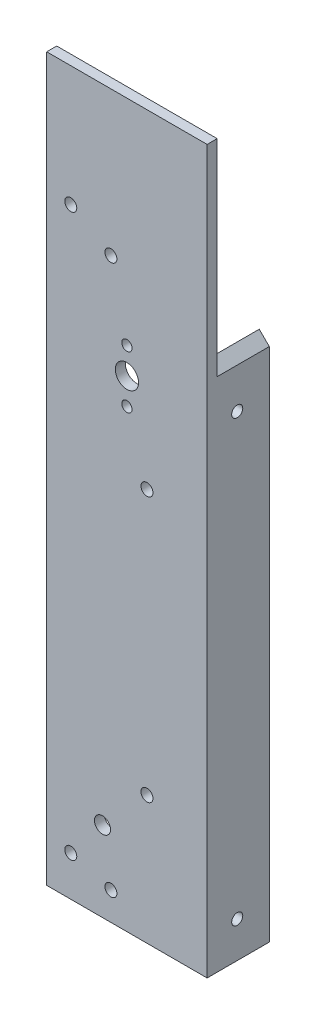
SolidWorks part; units mm, degrees
ref_plane "Front Plane" through (0, 0, 0) normal (0, 0, 1) x (1, 0, 0)
ref_plane "Top Plane" through (0, 0, 0) normal (0, 1, 0) x (1, 0, 0)
ref_plane "Right Plane" through (0, 0, 0) normal (1, 0, 0) x (0, 0, -1)
sketch "Sketch1" plane through (0, 0, 0) normal (0, 1, 0) x (1, 0, 0)
  line L0 (0, 0) -> (-50.8, 0)
  line L1 (-50.8, 0) -> (-50.8, 3.175)
  line L2 (-50.8, 3.175) -> (-3.175, 3.175)
  line L3 (-3.175, 3.175) -> (-3.175, 19.685)
  line L4 (-3.175, 19.685) -> (0, 19.685)
  line L5 (0, 19.685) -> (0, 0)
  dimension "D1" = 16.51
  dimension "D2" = 3.175
  dimension "D3" = 50.8
extrude "Boss-Extrude1" add sketch "Sketch1" along normal blind 203.2 contours L2 L3 L4 L5 L0 L1
sketch "Sketch4" plane through (0, 0, 0) normal (0, 0, 1) x (1, 0, 0)
  line L0 (0, 203.2) -> (0, 0) construction
  line L1 (-50.8, 214.122) -> (-57.2505, 214.122)
  line L2 (-50.8, 214.122) -> (0, 163.322)
  line L3 (-50.8, 203.2) -> (-50.8, 0) construction
  line L5 (14.4916, 163.322) -> (14.4916, 247.072)
  line L6 (14.4916, 247.072) -> (-57.2505, 247.072)
  line L7 (-57.2505, 247.072) -> (-57.2505, 214.122)
  line L9 (0, 163.322) -> (14.4916, 163.322)
  dimension "D1" = 163.322
  dimension "D2" = 135
extrude "Cut-Extrude2" cut sketch "Sketch4" against normal through all contours L7 L1 L2 L9 L5 L6
sketch "Sketch5" plane through (0, 0, 0) normal (0, 0, 1) x (1, 0, 0)
  line L0 (-25.4, 160.782) -> (-25.4, 144.018) construction
  line L1 (0, 0) -> (-50.8, 0) construction
  line L2 (0, 152.4) -> (-50.8, 152.4) construction
  line L3 (0, 163.322) -> (0, 0) construction
  line L4 (-50.8, 203.2) -> (-50.8, 0) construction
  circle A0 centre (-25.4, 152.4) radius 3.683
  circle A1 centre (-25.4, 160.782) radius 1.632
  circle A2 centre (-25.4, 144.018) radius 1.632
  point P4 (-25.4, 152.4)
  point P15 (-25.4, 152.4)
  dimension "D1" = 7.366
  dimension "D2" = 3.2639
  dimension "D3" = 152.4
  dimension "D4" = 16.764
extrude "Cut-Extrude3" cut sketch "Sketch5" against normal through all
sketch "Sketch6" plane through (0, 0, 0) normal (1, 0, 0) x (0, 0, -1)
  line L1 (19.685, 163.322) -> (0, 163.322) construction
  line L3 (19.685, 0) -> (0, 0) construction
  circle A0 centre (9.5305, 11.43) radius 1.7526
  circle A1 centre (9.5305, 150.622) radius 1.7526
  dimension "D1" = 3.5052
  dimension "D4" = 3.5052
  dimension "D2" = 11.43
  dimension "D3" = 12.7
extrude "Cut-Extrude4" cut sketch "Sketch6" against normal through all contours A1 | A0
sketch "Sketch7" plane through (0, 0, -3.175) normal (0, 0, -1) x (-1, 0, 0)
  circle A0 centre (30.48, 8.89) radius 1.7526
  circle A1 centre (30.48, 8.89) radius 1.7526 construction
  circle A2 centre (30.48, 182.88) radius 1.7526
  circle A3 centre (30.48, 182.88) radius 1.7526 construction
sketch "Sketch8" plane through (0, 0, -3.175) normal (0, 0, -1) x (-1, 0, 0)
  circle A0 centre (30.48, 8.89) radius 1.8986
  circle A1 centre (30.48, 8.89) radius 1.7526 construction
  circle A2 centre (30.48, 182.88) radius 1.8987
  circle A3 centre (30.48, 182.88) radius 1.7526 construction
  dimension "D1" = 3.7973
  dimension "D2" = 3.7973
extrude "Cut-Extrude5" cut sketch "Sketch8" against normal through all
sketch "Sketch9" plane through (0, 0, -3.175) normal (0, 0, -1) x (-1, 0, 0)
  line L0 (0, 163.322) -> (0, 0) construction
  line L2 (0, 0) -> (50.8, 0) construction
  circle A0 centre (19.05, 40.64) radius 1.8987
  circle A1 centre (19.05, 124.46) radius 1.8987
  dimension "D1" = 3.7973
  dimension "D2" = 19.05
  dimension "D3" = 83.82
  dimension "D4" = 40.64
extrude "Cut-Extrude6" cut sketch "Sketch9" against normal through all
sketch "Sketch10" plane through (0, 0, 0) normal (0, 0, 1) x (1, 0, 0)
  line L0 (0, 228.6) -> (0, 163.322)
  line L1 (-50.8, 203.2) -> (-39.878, 203.2)
  line L2 (-50.8, 203.2) -> (-50.8, 228.6)
  line L3 (-50.8, 228.6) -> (0, 228.6)
  line L5 (0, 163.322) -> (-39.878, 203.2)
  line L6 (-39.878, 203.2) -> (0, 163.322) construction
  dimension "D1" = 25.4
extrude "Boss-Extrude2" add sketch "Sketch10" against normal blind 3.175
sketch "Sketch11" plane through (0, 0, 0) normal (0, 0, 1) x (1, 0, 0)
  line L1 (-50.8, 228.6) -> (-50.8, 0) construction
  line L2 (0, 0) -> (-50.8, 0) construction
  circle A0 centre (-33.1362, 25.4) radius 2.54
  dimension "D3" = 5.08
  dimension "D1" = 17.6638
  dimension "D2" = 25.4
extrude "Cut-Extrude7" cut sketch "Sketch11" against normal through all
sketch "Sketch12" plane through (0, 0, -3.175) normal (0, 0, -1) x (-1, 0, 0)
  circle A0 centre (43.18, 12.7) radius 1.8986
  circle A1 centre (43.18, 190.4989) radius 1.8987
extrude "Cut-Extrude8" cut sketch "Sketch12" against normal through all
